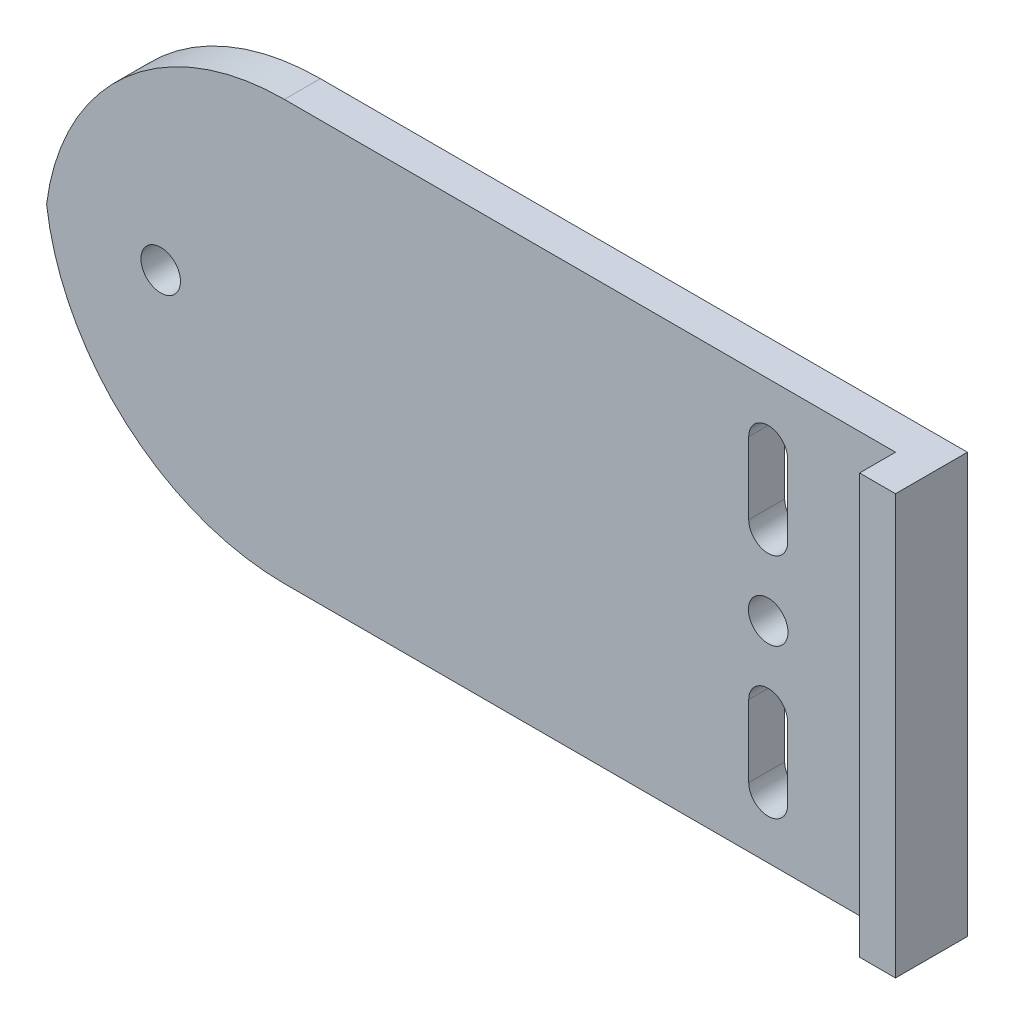
SolidWorks part; units mm, degrees
material "POM 乙缩醛共聚物"
ref_plane "前视基准面" through (0, 0, 0) normal (0, 0, 1) x (1, 0, 0)
ref_plane "上视基准面" through (0, 0, 0) normal (0, 1, 0) x (1, 0, 0)
ref_plane "右视基准面" through (0, 0, 0) normal (1, 0, 0) x (0, 0, -1)
sketch "草图1" plane through (0, 0, 0) normal (0, 0, 1) x (1, 0, 0)
  line L0 (0, 17.5) -> (50, 17.5)
  line L1 (50, 17.5) -> (50, -17.5)
  line L2 (50, -17.5) -> (0, -17.5)
  line L3 (34.75, 12.5) -> (34.75, 6.5)
  line L4 (38, 6.5) -> (38, 12.5)
  line L5 (34.75, -6.5) -> (34.75, -12.5)
  line L6 (38, -12.5) -> (38, -6.5)
  line L7 (0, 0) -> (-14.32, 0) construction
  line L8 (0, 17.5) -> (-24, 17.5)
  line L9 (-24, 17.5) -> (-24, -17.5)
  line L10 (-24, -17.5) -> (0, -17.5)
  arc A0 (0, 17.5) -> (0, -17.5) centre (0, 0) ccw construction
  circle A1 centre (0, 0) radius 1.65 construction
  arc A2 (34.75, 6.5) -> (38, 6.5) centre (36.375, 6.5) ccw
  arc A3 (38, 12.5) -> (34.75, 12.5) centre (36.375, 12.5) ccw
  arc A4 (34.75, -12.5) -> (38, -12.5) centre (36.375, -12.5) ccw
  arc A5 (38, -6.5) -> (34.75, -6.5) centre (36.375, -6.5) ccw
  circle A6 centre (36.375, 0) radius 1.65
  circle A7 centre (-14.32, 0) radius 1.65
  dimension "D1" = 17.5
  dimension "D3" = 3.3
  dimension "D4" = 3.25
  dimension "D11" = 3.3
  dimension "D13" = 3.3
  dimension "D2" = 50
  dimension "D5" = 6
  dimension "D6" = 6
  dimension "D7" = 12
  dimension "D8" = 5
  dimension "D9" = 12
  dimension "D10" = 5
  dimension "D12" = 14.32
  dimension "D14" = 24
extrude "凸台-拉伸1" add sketch "草图1" along normal blind 3
fillet "圆角1" radius 20 2 edges at (-24, -17.5, 1.5) (-24, 17.5, 1.5)
sketch "草图4" plane through (0, 0, 0) normal (0, 0, -1) x (-1, 0, 0)
  line L0 (-50, 17.5) -> (4, 17.5) construction
  line L1 (-50, -17.5) -> (-47, -17.5)
  line L2 (-50, -17.5) -> (-50, 17.5)
  line L3 (-50, 17.5) -> (-47, 17.5)
  line L4 (-47, -17.5) -> (-47, 17.5)
  dimension "D1" = 3
extrude "凸台-拉伸2" add sketch "草图4" against normal blind 6
